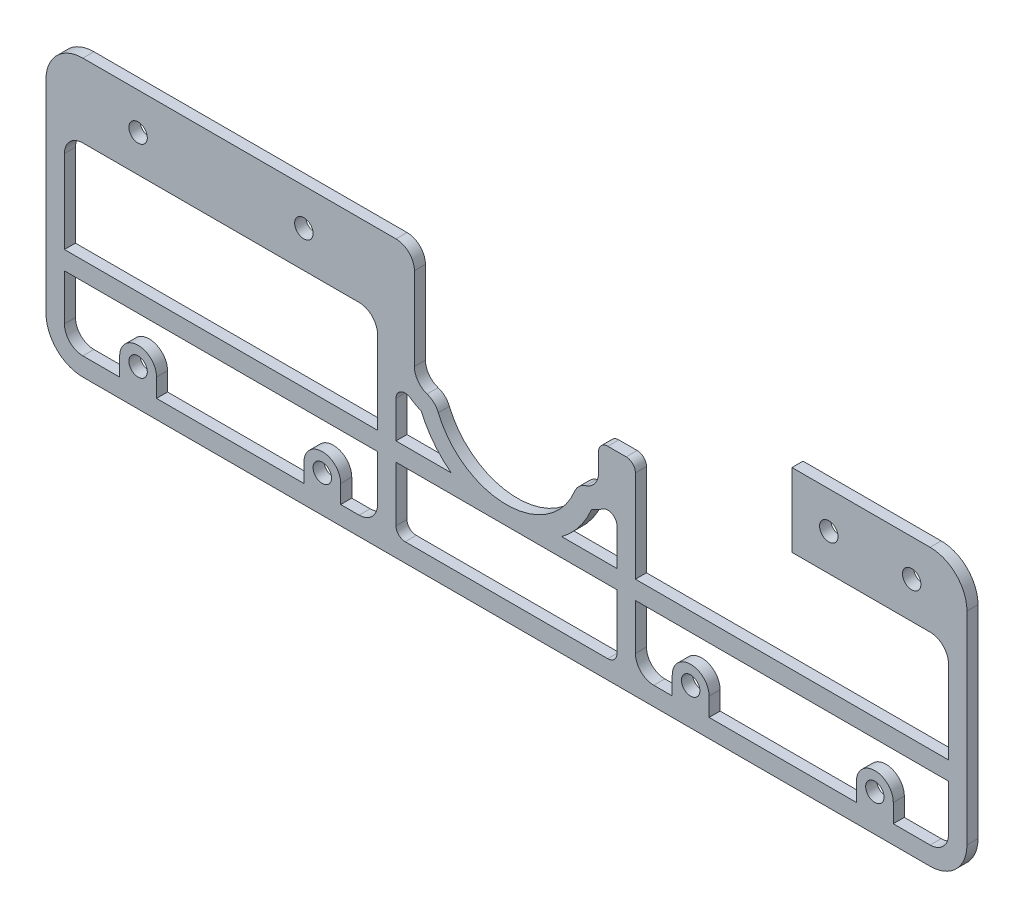
SolidWorks part; units mm, degrees
ref_plane "Front Plane" through (0, 0, 0) normal (0, 0, 1) x (1, 0, 0)
ref_plane "Top Plane" through (0, 0, 0) normal (0, 1, 0) x (1, 0, 0)
ref_plane "Right Plane" through (0, 0, 0) normal (1, 0, 0) x (0, 0, -1)
sketch "Sketch1" plane through (0, 0, 0) normal (0, 0, 1) x (1, 0, 0)
  line L0 (-40, 20) -> (-40, 55) construction
  line L4 (-250, -55) -> (-250, 3.1783)
  line L8 (-50, 75) -> (-230, 75) construction
  line L17 (0, -20) -> (0, -40)
  line L25 (0, -65) -> (0, -75)
  line L26 (0, 75) -> (0, -75) construction
  line L27 (-50, 95) -> (50, 95) construction
  line L34 (0, -75) -> (-230, -75)
  line L156 (-50, 75) -> (-230, 75) construction
  line L161 (0, -40) -> (0, -65)
  line L165 (-164.3309, 75) -> (-60, 75)
  line L167 (-230, 75) -> (-220, 75)
  line L171 (-250, 3.1783) -> (-250, 55)
  line L172 (-220, 75) -> (-164.3309, 75)
  line L173 (-50, 65) -> (-50, 20)
  arc A0 (-40, 20) -> (0, -20) centre (0, 20) ccw construction
  circle A1 centre (0, 20) radius 30 construction
  arc A4 (-230, -75) -> (-250, -55) centre (-230, -55) cw
  arc A5 (-250, 55) -> (-230, 75) centre (-230, 55) cw
  arc A124 (0, -20) -> (-37, 4.8013) centre (0, 20) cw
  arc A125 (-60, 75) -> (-50, 65) centre (-60, 65) cw
  arc A126 (-43.125, 10.5008) -> (-50, 20) centre (-40, 20) cw
  arc A127 (-37, 4.8013) -> (-43.125, 10.5008) centre (-46.25, 1.0016) ccw
  point P0 (0, 0)
  point P10 (-50, 10)
  point P11 (0, 50)
  point P30 (-40, 75)
  point P45 (0, -30)
  point P74 (0, 95)
  dimension "D3" = 80
  dimension "D4" = 60
  dimension "D6" = 55
  dimension "D7" = 75
  dimension "D10" = 10
  dimension "D11" = 20
  dimension "D8" = 10
  dimension "D5" = 10
  dimension "D9" = 20
  dimension "D13" = 210
  dimension "D16" = 100
  dimension "D17" = 20
  dimension "D26" = 250
extrude "Boss-Extrude1" add sketch "Sketch1" along normal blind 6
mirror "Mirror1" about plane through (0, -20, 6) normal (-1, 0, 0) of "Boss-Extrude1"
sketch "Sketch3" plane through (0, 0, 6) normal (0, 0, 1) x (1, 0, 0)
  line L0 (155, 75) -> (155, 35)
  line L1 (60, 75) -> (230, 75) construction
  line L2 (155, 35) -> (50, 35)
  line L3 (50, 20) -> (50, 65) construction
  line L4 (50, 20) -> (50, 65) construction
  line L5 (60, 75) -> (230, 75)
  line L6 (50, 65) -> (50, 35)
  line L7 (-60, 75) -> (-230, 75) construction
  line L8 (-250, 55) -> (-250, -55) construction
  line L9 (250, 55) -> (250, -55) construction
  arc A0 (60, 75) -> (50, 65) centre (60, 65) ccw construction
  arc A1 (60, 75) -> (50, 65) centre (60, 65) ccw
  circle A2 centre (175, 55) radius 5
  circle A3 centre (220, 55) radius 5
  circle A4 centre (-200, 55) radius 5
  circle A5 centre (-110, 55) radius 5
  line M15 (230, 75) -> (60, 75)
  arc M16 (60, 75) -> (50, 65) centre (60, 65) ccw
  line M17 (50, 65) -> (50, 20)
  dimension "D3" = 10
  dimension "D4" = 10
  dimension "D5" = 10
  dimension "D6" = 10
  dimension "D8" = 20
  dimension "D11" = 20
  dimension "D12" = 30
  dimension "D1" = 40
  dimension "D2" = 105
  dimension "D7" = 20
  dimension "D9" = 50
  dimension "D10" = 140
extrude "Cut-Extrude1" cut sketch "Sketch3" against normal through all contours L2 L0 M15 M16 M17 | A2 | A3 | A5 | A4 region at (102.7582, 54.9088, 6) region at (175, 55, 6) region at (220, 55, 6) region at (-110, 55, 6)
sketch "Sketch4" plane through (0, 0, 6) normal (0, 0, 1) x (1, 0, 0)
  line L0 (-230, -75) -> (230, -75) construction
  line L1 (-70, 25.101) -> (-70, -54.899)
  line L2 (-50, 20) -> (-50, 65) construction
  line L7 (-240, -55) -> (-240, 25.101)
  line L8 (-250, 55) -> (-250, -55) construction
  line L11 (-110, 35.101) -> (-80, 35.101)
  line L12 (-110, 35.101) -> (-140, 35.101)
  line L13 (-230, 35.101) -> (-140, 35.101)
  line L15 (-230, -65) -> (-210, -65)
  line L16 (-210, -65) -> (-210, -55)
  line L17 (-190, -55) -> (-190, -65)
  line L18 (-190, -65) -> (-110, -65)
  line L19 (-110, -65) -> (-110, -55)
  line L20 (-90, -55) -> (-90, -64.899)
  line L21 (-90, -64.899) -> (-80, -64.899)
  circle A1 centre (-200, -55) radius 5
  circle A2 centre (-100, -55) radius 5
  arc A6 (-230, -65) -> (-240, -55) centre (-230, -55) cw
  arc A12 (-210, -55) -> (-190, -55) centre (-200, -55) cw
  arc A13 (-110, -55) -> (-90, -55) centre (-100, -55) cw
  arc A14 (-240, 25.101) -> (-230, 35.101) centre (-230, 25.101) cw
  arc A15 (-70, -54.899) -> (-80, -64.899) centre (-80, -54.899) cw
  arc A16 (-70, 25.101) -> (-80, 35.101) centre (-80, 25.101) ccw
  point P0 (0, -75)
  dimension "D13" = 10
  dimension "D17" = 10
  dimension "D2" = 10
  dimension "D3" = 200
  dimension "D4" = 100
  dimension "D7" = 20
  dimension "D9" = 10
  dimension "D11" = 20
  dimension "D16" = 80
extrude "Cut-Extrude2" cut sketch "Sketch4" against normal through all contours L7 A6 L15 L16 | L13 | L17 L18 L19 | L20 L21 A15 L1 A16 L11 | A1 | A2 region at (-155.2296, -13.1384, 6) region at (-200, -55, 6) region at (-100, -55, 6)
mirror "Mirror2" about plane through (0, 0, 0) normal (1, 0, 0) of "Cut-Extrude2"
fillet "Fillet4" radius 5 1 edges at (50, 35, 3)
sketch "Sketch8" plane through (0, 0, 6) normal (0, 0, 1) x (1, 0, 0)
  line L0 (-60, 0) -> (-60, -64.899)
  line L2 (-60, -64.899) -> (60, -64.899)
  line L3 (60, -64.899) -> (60, 0)
  line L4 (-90, -64.899) -> (-80, -64.899) construction
  arc A0 (43.125, 10.5008) -> (50, 20) centre (40, 20) ccw construction
  arc A1 (43.125, 10.5008) -> (37, 4.8013) centre (46.25, 1.0016) ccw construction
  arc A2 (-37, 4.8013) -> (-43.125, 10.5008) centre (-46.25, 1.0016) ccw construction
  arc A3 (-50, 20) -> (-43.125, 10.5008) centre (-40, 20) ccw construction
  arc A4 (-37, 4.8013) -> (37, 4.8013) centre (0, 20) ccw construction
  arc A5 (43.125, 10.5008) -> (50, 20) centre (40, 20) ccw construction
  arc A6 (43.125, 10.5008) -> (37, 4.8013) centre (46.25, 1.0016) ccw construction
  arc A7 (-37, 4.8013) -> (-43.125, 10.5008) centre (-46.25, 1.0016) ccw construction
  arc A8 (-50, 20) -> (-43.125, 10.5008) centre (-40, 20) ccw construction
  arc A9 (-37, 4.8013) -> (37, 4.8013) centre (0, 20) ccw construction
  arc A10 (-52, 4) -> (-46.25, 1.0016) centre (-40, 20) ccw
  arc A11 (-46.25, 1.0016) -> (-46.25, 1.0016) centre (-46.25, 1.0016) ccw
  arc A12 (-46.25, 1.0016) -> (46.25, 1.0016) centre (0, 20) ccw
  arc A13 (46.25, 1.0016) -> (46.25, 1.0016) centre (46.25, 1.0016) ccw
  arc A14 (46.25, 1.0016) -> (52, 4) centre (40, 20) ccw
  arc A15 (46.25, 1.0016) -> (60, 20) centre (40, 20) ccw construction
  arc A16 (60, 0) -> (52, 4) centre (55, 0) ccw
  arc A17 (-60, 20) -> (-46.25, 1.0016) centre (-40, 20) ccw construction
  arc A18 (-60, 0) -> (-52, 4) centre (-55, 0) cw
  dimension "D2" = 5
  dimension "D1" = 10
extrude "Cut-Extrude5" cut sketch "Sketch8" against normal through all
fillet "Fillet5" radius 5 1 edges at (-60, -64.899, 3)
fillet "Fillet6" radius 5 1 edges at (60, -64.899, 3)
sketch "Sketch9" plane through (0, 0, 6) normal (0, 0, 1) x (1, 0, 0)
  line L0 (78.5825, 35) -> (55, 35) construction
  line L1 (78.5825, 35) -> (70, 35)
  line L2 (70, 25.101) -> (70, 35)
  arc A0 (78.5825, 35) -> (70, 25.101) centre (80, 25.101) ccw construction
  arc A1 (78.5825, 35) -> (70, 25.101) centre (80, 25.101) ccw
extrude "Cut-Extrude6" cut sketch "Sketch9" against normal through all
fillet "Fillet7" radius 5 1 edges at (70, 35, 3)
sketch "Sketch10" plane through (0, 0, 6) normal (0, 0, 1) x (1, 0, 0)
  line L0 (-250, -20) -> (250, -20)
  line L1 (-250, 55) -> (-250, -55) construction
  line L2 (250, 55) -> (250, -55) construction
  line L3 (250, -20) -> (250, -30)
  line L4 (250, -30) -> (-250, -30)
  line L5 (-250, -30) -> (-250, -20)
  arc A0 (-37, 4.8013) -> (37, 4.8013) centre (0, 20) ccw construction
  arc A1 (-46.25, 1.0016) -> (46.25, 1.0016) centre (0, 20) ccw construction
extrude "Boss-Extrude2" add sketch "Sketch10" against normal up to surface (6 mm away) up to face at (75.9484, -5.9001, 0)
